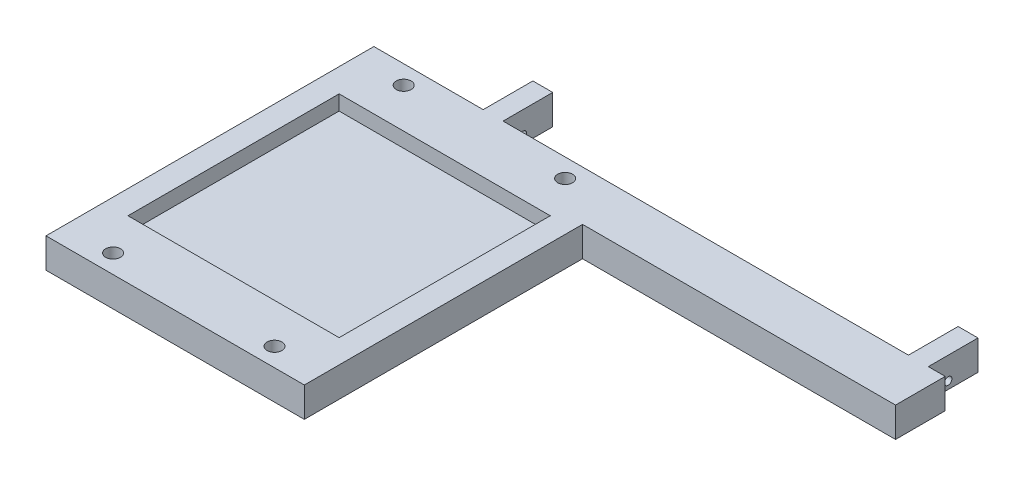
SolidWorks part; units mm, degrees
ref_plane "Front Plane" through (0, 0, 0) normal (0, 0, 1) x (1, 0, 0)
ref_plane "Top Plane" through (0, 0, 0) normal (0, 1, 0) x (1, 0, 0)
ref_plane "Right Plane" through (0, 0, 0) normal (1, 0, 0) x (0, 0, -1)
sketch "Sketch1" plane through (0, 0, 0) normal (0, 1, 0) x (1, 0, 0)
  line L1 (0, 0) -> (-52, 0)
  line L2 (0, 0) -> (0, -66)
  line L3 (0, -66) -> (-52, -66)
  line L4 (-52, 0) -> (-52, -66)
  dimension "D1" = 66
  dimension "D2" = 52
extrude "Boss-Extrude1" add sketch "Sketch1" along normal blind 6
sketch "Sketch2" plane through (0, 6, 0) normal (0, 1, 0) x (1, 0, 0)
  line L0 (-52, 0) -> (-52, -66) construction
  line L1 (-47.25, -11.75) -> (-4.75, -11.75)
  line L2 (-47.25, -11.75) -> (-47.25, -54.25)
  line L3 (-47.25, -54.25) -> (-4.75, -54.25)
  line L4 (-4.75, -11.75) -> (-4.75, -54.25)
  line L5 (-52, -66) -> (0, -66) construction
  point P6 (-47.25, -33)
  point P7 (-52, -33)
  point P8 (-26, -54.25)
  point P11 (-26, -66)
  dimension "D1" = 42.5
  dimension "D2" = 42.5
  dimension "D3" = 0
  dimension "D4" = 0
extrude "Cut-Extrude1" cut sketch "Sketch2" against normal blind 3
sketch "Sketch3" plane through (0, 6, 0) normal (0, 1, 0) x (1, 0, 0)
  line L0 (-4.75, -11.75) -> (-47.25, -11.75) construction
  line L1 (-47.25, -11.75) -> (-47.25, -54.25) construction
  line L2 (-26, 0) -> (-26, -78.9032) construction
  line L3 (0, 0) -> (-52, 0) construction
  line L4 (-52, -33) -> (19.2006, -33) construction
  line L5 (-52, 0) -> (-52, -66) construction
  circle A0 centre (-42.25, -3.75) radius 1.5
  circle A1 centre (-9.75, -3.75) radius 1.5
  circle A2 centre (-9.75, -62.25) radius 1.5
  circle A3 centre (-42.25, -62.25) radius 1.5
  dimension "D1" = 8
  dimension "D2" = 3
  dimension "D3" = 5
extrude "Cut-Extrude2" cut sketch "Sketch3" against normal blind 13
sketch "Sketch4" plane through (0, 0, 0) normal (1, 0, 0) x (0, 0, -1)
  line L0 (-66, 6) -> (0, 6) construction
  line L1 (0, 0) -> (-10, 0)
  line L2 (0, 0) -> (0, 6)
  line L3 (0, 6) -> (-10, 6)
  line L4 (-10, 0) -> (-10, 6)
  dimension "D1" = 10
extrude "Boss-Extrude2" add sketch "Sketch4" along normal blind 63
sketch "Sketch5" plane through (0, 0, 0) normal (0, 0, -1) x (-1, 0, 0)
  line L0 (-63, 6) -> (52, 6) construction
  line L1 (30, 6) -> (26, 6)
  line L2 (30, 6) -> (30, 0)
  line L3 (30, 0) -> (26, 0)
  line L4 (26, 6) -> (26, 0)
  line L5 (-63, 0) -> (52, 0) construction
  line L6 (52, 6) -> (52, 0) construction
  line L8 (-55.6, 6) -> (-59.6, 6)
  line L9 (-55.6, 6) -> (-55.6, 0)
  line L10 (-55.6, 0) -> (-59.6, 0)
  line L11 (-59.6, 6) -> (-59.6, 0)
  point P14 (-57.6, 0)
  point P15 (28, 0)
  dimension "D1" = 4
  dimension "D2" = 22
  dimension "D3" = 4
  dimension "D4" = 85.6
extrude "Boss-Extrude3" add sketch "Sketch5" along normal blind 10
sketch "Sketch6" plane through (59.6, 0, 0) normal (1, 0, 0) x (0, 0, -1)
  line L0 (10, 0) -> (0, 0) construction
  line L1 (0, 6) -> (0, 0) construction
  circle A0 centre (4, 1.5) radius 0.75
  dimension "D1" = 1.5
  dimension "D2" = 4
  dimension "D3" = 1.5
extrude "Cut-Extrude3" cut sketch "Sketch6" against normal blind 114
